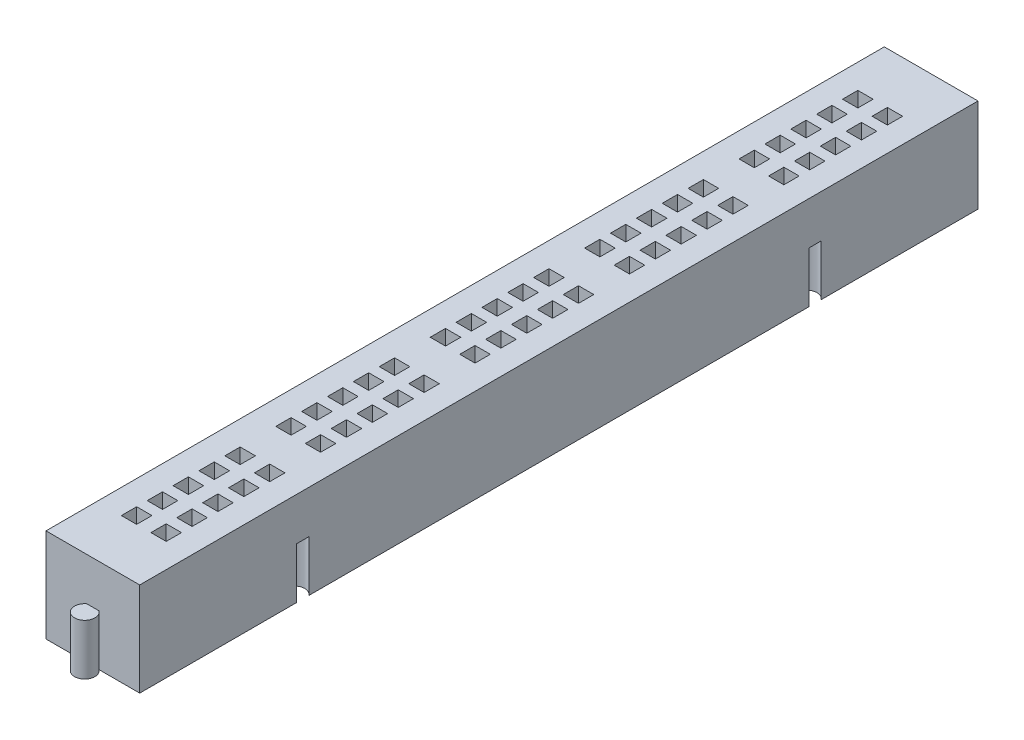
SolidWorks part; units mm, degrees
ref_plane "Front Plane" through (0, 0, 0) normal (0, 0, 1) x (1, 0, 0)
ref_plane "Top Plane" through (0, 0, 0) normal (0, 1, 0) x (1, 0, 0)
ref_plane "Right Plane" through (0, 0, 0) normal (1, 0, 0) x (0, 0, -1)
sketch "Sketch1" plane through (0, 0, 0) normal (0, 1, 0) x (1, 0, 0)
  line L1 (-6.5835, 43.2908) -> (2.6165, 43.2908)
  line L2 (-6.5835, 43.2908) -> (-6.5835, -39.0092)
  line L3 (-6.5835, -39.0092) -> (2.6165, -39.0092)
  line L4 (2.6165, 43.2908) -> (2.6165, -39.0092)
  dimension "D1" = 82.3
  dimension "D2" = 9.2
extrude "Boss-Extrude1" add sketch "Sketch1" along normal blind 9.2
sketch "Sketch2" plane through (0, 9.2, 0) normal (0, 1, 0) x (1, 0, 0)
  line L0 (-6.5835, 43.2908) -> (-6.5835, -39.0092) construction
  line L1 (-4.1835, 38.2908) -> (-2.6835, 38.2908)
  line L2 (-4.1835, 38.2908) -> (-4.1835, 36.7908)
  line L3 (-4.1835, 36.7908) -> (-2.6835, 36.7908)
  line L4 (-2.6835, 38.2908) -> (-2.6835, 36.7908)
  line L5 (2.6165, 43.2908) -> (-6.5835, 43.2908) construction
  line L6 (-1.2835, 38.2908) -> (-1.2835, 36.7908)
  line L7 (-1.2835, 38.2908) -> (0.2165, 38.2908)
  line L8 (0.2165, 38.2908) -> (0.2165, 36.7908)
  line L9 (-1.2835, 36.7908) -> (0.2165, 36.7908)
  line L10 (2.6165, -39.0092) -> (2.6165, 43.2908) construction
  line L11 (-4.1835, 35.7508) -> (-4.1835, 34.2508)
  line L12 (-4.1835, 35.7508) -> (-2.6835, 35.7508)
  line L13 (-2.6835, 35.7508) -> (-2.6835, 34.2508)
  line L14 (-4.1835, 34.2508) -> (-2.6835, 34.2508)
  line L15 (-1.2835, 35.7508) -> (-1.2835, 34.2508)
  line L16 (-1.2835, 34.2508) -> (0.2165, 34.2508)
  line L17 (0.2165, 35.7508) -> (0.2165, 34.2508)
  line L18 (-1.2835, 35.7508) -> (0.2165, 35.7508)
  line L19 (-4.1835, 33.2108) -> (-4.1835, 31.7108)
  line L20 (-4.1835, 33.2108) -> (-2.6835, 33.2108)
  line L21 (-2.6835, 33.2108) -> (-2.6835, 31.7108)
  line L22 (-4.1835, 31.7108) -> (-2.6835, 31.7108)
  line L23 (-1.2835, 33.2108) -> (-1.2835, 31.7108)
  line L24 (-1.2835, 31.7108) -> (0.2165, 31.7108)
  line L25 (0.2165, 33.2108) -> (0.2165, 31.7108)
  line L26 (-1.2835, 33.2108) -> (0.2165, 33.2108)
  line L27 (-4.1835, 30.6708) -> (-4.1835, 29.1708)
  line L28 (-4.1835, 30.6708) -> (-2.6835, 30.6708)
  line L29 (-2.6835, 30.6708) -> (-2.6835, 29.1708)
  line L30 (-4.1835, 29.1708) -> (-2.6835, 29.1708)
  line L31 (-1.2835, 30.6708) -> (-1.2835, 29.1708)
  line L32 (-1.2835, 29.1708) -> (0.2165, 29.1708)
  line L33 (0.2165, 30.6708) -> (0.2165, 29.1708)
  line L34 (-1.2835, 30.6708) -> (0.2165, 30.6708)
  line L35 (-4.1835, 28.1308) -> (-4.1835, 26.6308)
  line L36 (-4.1835, 28.1308) -> (-2.6835, 28.1308)
  line L37 (-2.6835, 28.1308) -> (-2.6835, 26.6308)
  line L38 (-4.1835, 26.6308) -> (-2.6835, 26.6308)
  line L39 (-1.2835, 28.1308) -> (-1.2835, 26.6308)
  line L40 (-1.2835, 26.6308) -> (0.2165, 26.6308)
  line L41 (0.2165, 28.1308) -> (0.2165, 26.6308)
  line L42 (-1.2835, 28.1308) -> (0.2165, 28.1308)
  line L43 (-4.1835, 23.1308) -> (-4.1835, 21.6308)
  line L44 (-4.1835, 23.1308) -> (-2.6835, 23.1308)
  line L45 (-2.6835, 23.1308) -> (-2.6835, 21.6308)
  line L46 (-4.1835, 21.6308) -> (-2.6835, 21.6308)
  line L47 (-1.2835, 23.1308) -> (-1.2835, 21.6308)
  line L48 (-1.2835, 21.6308) -> (0.2165, 21.6308)
  line L49 (0.2165, 23.1308) -> (0.2165, 21.6308)
  line L50 (-1.2835, 23.1308) -> (0.2165, 23.1308)
  line L51 (-1.2835, 20.5908) -> (-1.2835, 19.0908)
  line L52 (-1.2835, 19.0908) -> (0.2165, 19.0908)
  line L53 (0.2165, 20.5908) -> (0.2165, 19.0908)
  line L54 (-1.2835, 20.5908) -> (0.2165, 20.5908)
  line L55 (-4.1835, 20.5908) -> (-4.1835, 19.0908)
  line L56 (-4.1835, 19.0908) -> (-2.6835, 19.0908)
  line L57 (-2.6835, 20.5908) -> (-2.6835, 19.0908)
  line L58 (-4.1835, 20.5908) -> (-2.6835, 20.5908)
  line L59 (-4.1835, 18.0508) -> (-4.1835, 16.5508)
  line L60 (-4.1835, 16.5508) -> (-2.6835, 16.5508)
  line L61 (-2.6835, 18.0508) -> (-2.6835, 16.5508)
  line L62 (-4.1835, 18.0508) -> (-2.6835, 18.0508)
  line L63 (-1.2835, 18.0508) -> (-1.2835, 16.5508)
  line L64 (-1.2835, 16.5508) -> (0.2165, 16.5508)
  line L65 (0.2165, 18.0508) -> (0.2165, 16.5508)
  line L66 (-1.2835, 18.0508) -> (0.2165, 18.0508)
  line L67 (-1.2835, 15.5108) -> (-1.2835, 14.0108)
  line L68 (-1.2835, 14.0108) -> (0.2165, 14.0108)
  line L69 (0.2165, 15.5108) -> (0.2165, 14.0108)
  line L70 (-1.2835, 15.5108) -> (0.2165, 15.5108)
  line L71 (-4.1835, 15.5108) -> (-4.1835, 14.0108)
  line L72 (-4.1835, 14.0108) -> (-2.6835, 14.0108)
  line L73 (-2.6835, 15.5108) -> (-2.6835, 14.0108)
  line L74 (-4.1835, 15.5108) -> (-2.6835, 15.5108)
  line L75 (-4.1835, 12.9708) -> (-4.1835, 11.4708)
  line L76 (-4.1835, 11.4708) -> (-2.6835, 11.4708)
  line L77 (-2.6835, 12.9708) -> (-2.6835, 11.4708)
  line L78 (-4.1835, 12.9708) -> (-2.6835, 12.9708)
  line L79 (-1.2835, 12.9708) -> (-1.2835, 11.4708)
  line L80 (-1.2835, 11.4708) -> (0.2165, 11.4708)
  line L81 (0.2165, 12.9708) -> (0.2165, 11.4708)
  line L82 (-1.2835, 12.9708) -> (0.2165, 12.9708)
  line L83 (-4.1835, 7.9708) -> (-4.1835, 6.4708)
  line L84 (-4.1835, 7.9708) -> (-2.6835, 7.9708)
  line L85 (-2.6835, 7.9708) -> (-2.6835, 6.4708)
  line L86 (-4.1835, 6.4708) -> (-2.6835, 6.4708)
  line L87 (-1.2835, 7.9708) -> (-1.2835, 6.4708)
  line L88 (-1.2835, 6.4708) -> (0.2165, 6.4708)
  line L89 (0.2165, 7.9708) -> (0.2165, 6.4708)
  line L90 (-1.2835, 7.9708) -> (0.2165, 7.9708)
  line L91 (-1.2835, 5.4308) -> (-1.2835, 3.9308)
  line L92 (-1.2835, 3.9308) -> (0.2165, 3.9308)
  line L93 (0.2165, 5.4308) -> (0.2165, 3.9308)
  line L94 (-1.2835, 5.4308) -> (0.2165, 5.4308)
  line L95 (-4.1835, 5.4308) -> (-4.1835, 3.9308)
  line L96 (-4.1835, 3.9308) -> (-2.6835, 3.9308)
  line L97 (-2.6835, 5.4308) -> (-2.6835, 3.9308)
  line L98 (-4.1835, 5.4308) -> (-2.6835, 5.4308)
  line L99 (-4.1835, 2.8908) -> (-4.1835, 1.3908)
  line L100 (-4.1835, 1.3908) -> (-2.6835, 1.3908)
  line L101 (-2.6835, 2.8908) -> (-2.6835, 1.3908)
  line L102 (-4.1835, 2.8908) -> (-2.6835, 2.8908)
  line L103 (-1.2835, 2.8908) -> (-1.2835, 1.3908)
  line L104 (-1.2835, 1.3908) -> (0.2165, 1.3908)
  line L105 (0.2165, 2.8908) -> (0.2165, 1.3908)
  line L106 (-1.2835, 2.8908) -> (0.2165, 2.8908)
  line L107 (-1.2835, 0.3508) -> (-1.2835, -1.1492)
  line L108 (-1.2835, -1.1492) -> (0.2165, -1.1492)
  line L109 (0.2165, 0.3508) -> (0.2165, -1.1492)
  line L110 (-1.2835, 0.3508) -> (0.2165, 0.3508)
  line L111 (-4.1835, 0.3508) -> (-4.1835, -1.1492)
  line L112 (-4.1835, -1.1492) -> (-2.6835, -1.1492)
  line L113 (-2.6835, 0.3508) -> (-2.6835, -1.1492)
  line L114 (-4.1835, 0.3508) -> (-2.6835, 0.3508)
  line L115 (-4.1835, -2.1892) -> (-4.1835, -3.6892)
  line L116 (-4.1835, -3.6892) -> (-2.6835, -3.6892)
  line L117 (-2.6835, -2.1892) -> (-2.6835, -3.6892)
  line L118 (-4.1835, -2.1892) -> (-2.6835, -2.1892)
  line L119 (-1.2835, -2.1892) -> (-1.2835, -3.6892)
  line L120 (-1.2835, -3.6892) -> (0.2165, -3.6892)
  line L121 (0.2165, -2.1892) -> (0.2165, -3.6892)
  line L122 (-1.2835, -2.1892) -> (0.2165, -2.1892)
  line L123 (-4.1835, -7.1892) -> (-4.1835, -8.6892)
  line L124 (-4.1835, -7.1892) -> (-2.6835, -7.1892)
  line L125 (-2.6835, -7.1892) -> (-2.6835, -8.6892)
  line L126 (-4.1835, -8.6892) -> (-2.6835, -8.6892)
  line L127 (-1.2835, -7.1892) -> (-1.2835, -8.6892)
  line L128 (-1.2835, -8.6892) -> (0.2165, -8.6892)
  line L129 (0.2165, -7.1892) -> (0.2165, -8.6892)
  line L130 (-1.2835, -7.1892) -> (0.2165, -7.1892)
  line L131 (-1.2835, -9.7292) -> (-1.2835, -11.2292)
  line L132 (-1.2835, -11.2292) -> (0.2165, -11.2292)
  line L133 (0.2165, -9.7292) -> (0.2165, -11.2292)
  line L134 (-1.2835, -9.7292) -> (0.2165, -9.7292)
  line L135 (-4.1835, -9.7292) -> (-4.1835, -11.2292)
  line L136 (-4.1835, -11.2292) -> (-2.6835, -11.2292)
  line L137 (-2.6835, -9.7292) -> (-2.6835, -11.2292)
  line L138 (-4.1835, -9.7292) -> (-2.6835, -9.7292)
  line L139 (-4.1835, -12.2692) -> (-4.1835, -13.7692)
  line L140 (-4.1835, -13.7692) -> (-2.6835, -13.7692)
  line L141 (-2.6835, -12.2692) -> (-2.6835, -13.7692)
  line L142 (-4.1835, -12.2692) -> (-2.6835, -12.2692)
  line L143 (-1.2835, -12.2692) -> (-1.2835, -13.7692)
  line L144 (-1.2835, -13.7692) -> (0.2165, -13.7692)
  line L145 (0.2165, -12.2692) -> (0.2165, -13.7692)
  line L146 (-1.2835, -12.2692) -> (0.2165, -12.2692)
  line L147 (-1.2835, -14.8092) -> (-1.2835, -16.3092)
  line L148 (-1.2835, -16.3092) -> (0.2165, -16.3092)
  line L149 (0.2165, -14.8092) -> (0.2165, -16.3092)
  line L150 (-1.2835, -14.8092) -> (0.2165, -14.8092)
  line L151 (-4.1835, -14.8092) -> (-4.1835, -16.3092)
  line L152 (-4.1835, -16.3092) -> (-2.6835, -16.3092)
  line L153 (-2.6835, -14.8092) -> (-2.6835, -16.3092)
  line L154 (-4.1835, -14.8092) -> (-2.6835, -14.8092)
  line L155 (-4.1835, -17.3492) -> (-4.1835, -18.8492)
  line L156 (-4.1835, -18.8492) -> (-2.6835, -18.8492)
  line L157 (-2.6835, -17.3492) -> (-2.6835, -18.8492)
  line L158 (-4.1835, -17.3492) -> (-2.6835, -17.3492)
  line L159 (-1.2835, -17.3492) -> (-1.2835, -18.8492)
  line L160 (-1.2835, -18.8492) -> (0.2165, -18.8492)
  line L161 (0.2165, -17.3492) -> (0.2165, -18.8492)
  line L162 (-1.2835, -17.3492) -> (0.2165, -17.3492)
  line L163 (-4.1835, -22.3492) -> (-4.1835, -23.8492)
  line L164 (-4.1835, -22.3492) -> (-2.6835, -22.3492)
  line L165 (-2.6835, -22.3492) -> (-2.6835, -23.8492)
  line L166 (-4.1835, -23.8492) -> (-2.6835, -23.8492)
  line L167 (-1.2835, -22.3492) -> (-1.2835, -23.8492)
  line L168 (-1.2835, -23.8492) -> (0.2165, -23.8492)
  line L169 (0.2165, -22.3492) -> (0.2165, -23.8492)
  line L170 (-1.2835, -22.3492) -> (0.2165, -22.3492)
  line L171 (-1.2835, -24.8892) -> (-1.2835, -26.3892)
  line L172 (-1.2835, -26.3892) -> (0.2165, -26.3892)
  line L173 (0.2165, -24.8892) -> (0.2165, -26.3892)
  line L174 (-1.2835, -24.8892) -> (0.2165, -24.8892)
  line L175 (-4.1835, -24.8892) -> (-4.1835, -26.3892)
  line L176 (-4.1835, -26.3892) -> (-2.6835, -26.3892)
  line L177 (-2.6835, -24.8892) -> (-2.6835, -26.3892)
  line L178 (-4.1835, -24.8892) -> (-2.6835, -24.8892)
  line L179 (-4.1835, -27.4292) -> (-4.1835, -28.9292)
  line L180 (-4.1835, -28.9292) -> (-2.6835, -28.9292)
  line L181 (-2.6835, -27.4292) -> (-2.6835, -28.9292)
  line L182 (-4.1835, -27.4292) -> (-2.6835, -27.4292)
  line L183 (-1.2835, -27.4292) -> (-1.2835, -28.9292)
  line L184 (-1.2835, -28.9292) -> (0.2165, -28.9292)
  line L185 (0.2165, -27.4292) -> (0.2165, -28.9292)
  line L186 (-1.2835, -27.4292) -> (0.2165, -27.4292)
  line L187 (-1.2835, -29.9692) -> (-1.2835, -31.4692)
  line L188 (-1.2835, -31.4692) -> (0.2165, -31.4692)
  line L189 (0.2165, -29.9692) -> (0.2165, -31.4692)
  line L190 (-1.2835, -29.9692) -> (0.2165, -29.9692)
  line L191 (-4.1835, -29.9692) -> (-4.1835, -31.4692)
  line L192 (-4.1835, -31.4692) -> (-2.6835, -31.4692)
  line L193 (-2.6835, -29.9692) -> (-2.6835, -31.4692)
  line L194 (-4.1835, -29.9692) -> (-2.6835, -29.9692)
  line L195 (-4.1835, -32.5092) -> (-4.1835, -34.0092)
  line L196 (-4.1835, -34.0092) -> (-2.6835, -34.0092)
  line L197 (-2.6835, -32.5092) -> (-2.6835, -34.0092)
  line L198 (-4.1835, -32.5092) -> (-2.6835, -32.5092)
  line L199 (-1.2835, -32.5092) -> (-1.2835, -34.0092)
  line L200 (-1.2835, -34.0092) -> (0.2165, -34.0092)
  line L201 (0.2165, -32.5092) -> (0.2165, -34.0092)
  line L202 (-1.2835, -32.5092) -> (0.2165, -32.5092)
  line L203 (-6.5835, -39.0092) -> (2.6165, -39.0092) construction
  point P6 (-3.4335, 38.2908)
  point P15 (-3.4335, 29.1708)
  dimension "D1" = 1.5
  dimension "D2" = 1.5
  dimension "D3" = 2.4
  dimension "D4" = 5
  dimension "D6" = 2.4
  dimension "D8" = 1.04
  dimension "D10" = 5
  dimension "D5" = 2
  dimension "D7" = 5
  dimension "D9" = 5
extrude "Cut-Extrude1" cut sketch "Sketch2" against normal blind 8
sketch "Sketch3" plane through (0, 0, 0) normal (0, -1, 0) x (1, 0, 0)
  line L0 (-6.5835, 39.0092) -> (2.6165, 39.0092) construction
  line L1 (2.6165, 39.0092) -> (2.6165, -43.2908) construction
  line L2 (-6.5835, -43.2908) -> (-6.5835, 39.0092) construction
  line L3 (2.6165, -43.2908) -> (-6.5835, -43.2908) construction
  line L4 (-1.9835, -43.2908) -> (-1.9835, 39.0092) construction
  circle A0 centre (1.8165, 23.0092) radius 1
  circle A1 centre (1.8165, -27.2908) radius 1
  circle A2 centre (-7.3835, -27.2908) radius 1
  circle A3 centre (-7.3835, 23.0092) radius 1
  circle A4 centre (-1.9835, 39.8092) radius 1
  circle A5 centre (-1.9835, -42.4908) radius 1
  point P22 (-3.0245, 39.8092)
  point P23 (-1.6164, -42.4908)
  dimension "D1" = 2
  dimension "D2" = 2
  dimension "D3" = 2
  dimension "D4" = 2
  dimension "D5" = 2
  dimension "D6" = 2
  dimension "D7" = 0.8
  dimension "D8" = 0.8
  dimension "D9" = 0.8
  dimension "D10" = 0.8
  dimension "D11" = 0.8
  dimension "D12" = 0.8
  dimension "D13" = 16
  dimension "D14" = 16
  dimension "D15" = 16
  dimension "D16" = 16
  dimension "D17" = 0
  dimension "D18" = 0
extrude "Boss-Extrude2" add sketch "Sketch3" against normal blind 5 contours A2 | A3 | A4
extrude "Cut-Extrude2" cut sketch "Sketch3<3>" against normal blind 5 contours A0 | A1 | A5
sketch "Sketch3<3>" plane through (0, 0, 0) normal (0, -1, 0) x (1, 0, 0) same geometry as "Sketch3"
